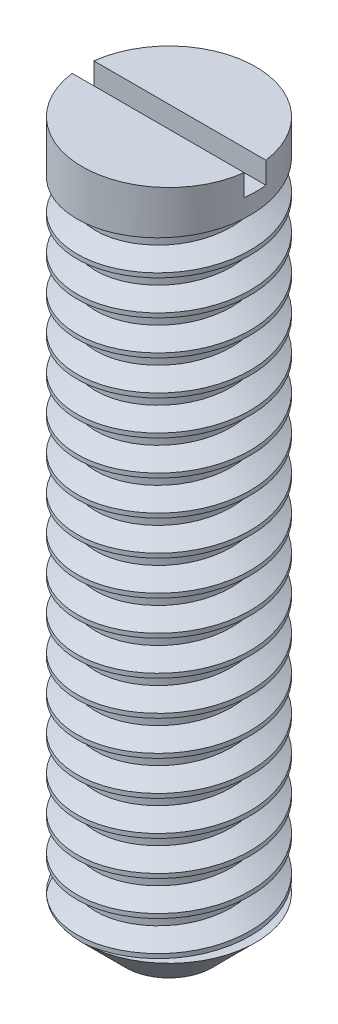
SolidWorks part; units mm, degrees
ref_plane "Front Plane" through (0, 0, 0) normal (0, 0, 1) x (1, 0, 0)
ref_plane "Top Plane" through (0, 0, 0) normal (0, 1, 0) x (1, 0, 0)
ref_plane "Right Plane" through (0, 0, 0) normal (1, 0, 0) x (0, 0, -1)
sketch "Sketch1" plane through (0, 0, 0) normal (0, 1, 0) x (1, 0, 0)
  circle A0 centre (0, 0) radius 2
extrude "Boss-Extrude1" add sketch "Sketch1" along normal blind 15
thread "Thread1" pitch 0.8 method cut profile "Thread Profile1" start angle 0, offset 0, length 15, pitch 0.8, diameter 4
ref_plane "Plane1" through (-2, 15, 0) normal (0, 0, 1) x (-1, 0, 0)
sketch "Thread Profile1" plane through (-2, 15, 0) normal (0, 0, 1) x (-1, 0, 0)
  line L0 (0, 0) -> (0, 0.8) construction
  line L11 (0, 0) -> (0, 0.7)
  line L12 (0, 0.7) -> (-0.433, 0.45)
  line L13 (-0.433, 0.45) -> (-0.433, 0.25)
  line L15 (-0.433, 0.25) -> (0, 0)
  line L17 (-0.433, 0.35) -> (0, 0.35) construction
  point P2 (0, 0)
  dimension "Pitch" = 0.8
  dimension "Profile_Angle" = 60
  dimension "Profile_Land" = 0.2
  dimension "Profile_Height" = 0.433
sketch "Sketch4" plane through (0, 15, 0) normal (0, 1, 0) x (1, 0, 0)
  line L0 (-2, 0) -> (2, 0)
  line L1 (-2, -0.25) -> (2, -0.25)
  line L2 (-2, 0.25) -> (2, 0.25)
  line L3 (2, -0.25) -> (2, 0.25)
  circle A0 centre (0, 0) radius 2 construction
  circle A1 centre (0, 0) radius 2
  dimension "D1" = 0.25
  dimension "D2" = 0.25
extrude "Boss-Extrude2" add sketch "Sketch4" along normal blind 0.5 contours A0 L2 | L1 A0 region at (0, 15, -0.9854) region at (0, 15, 0.9854)
sketch "Sketch5" plane through (0, 0, 0) normal (0, -1, 0) x (1, 0, 0)
  circle A0 centre (0, 0) radius 2
extrude "Boss-Extrude3" add sketch "Sketch5" along normal blind 1 draft 45
